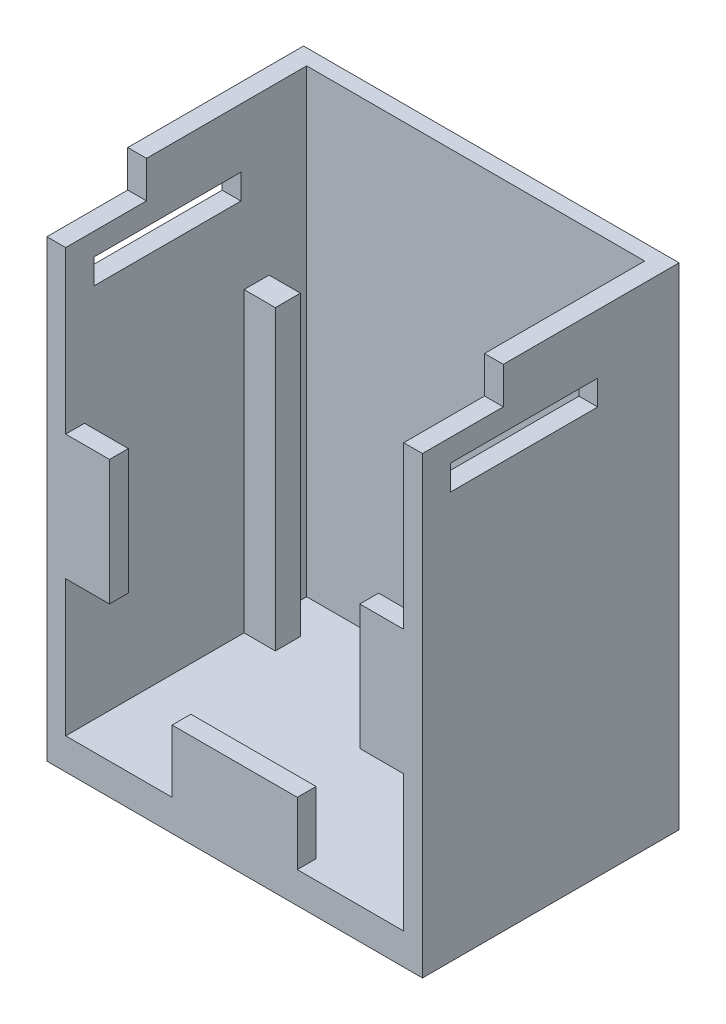
SolidWorks part; units mm, degrees
material "ABS"
ref_plane "Front Plane" through (0, 0, 0) normal (0, 0, 1) x (1, 0, 0)
ref_plane "Top Plane" through (0, 0, 0) normal (0, 1, 0) x (1, 0, 0)
ref_plane "Right Plane" through (0, 0, 0) normal (1, 0, 0) x (0, 0, -1)
sketch "Sketch1" plane through (0, 0, 0) normal (0, 0, 1) x (1, 0, 0)
  line L1 (15.24, -25.4) -> (-15.24, -25.4)
  line L2 (15.24, -25.4) -> (15.24, 15.24)
  line L3 (15.24, 15.24) -> (-15.24, 15.24)
  line L4 (-15.24, -25.4) -> (-15.24, 15.24)
  point P0 (0, 0)
  dimension "D1" = 30.48
  dimension "D2" = 40.64
extrude "Initial Block" add sketch "Sketch1" along normal blind 19.05 and the other way blind 1.778
sketch "Sketch2" plane through (0, 15.24, 0) normal (0, 1, 0) x (1, 0, 0)
  line L0 (15.24, 1.778) -> (-15.24, 1.778) construction
  line L1 (-13.716, 0.508) -> (13.716, 0.508)
  line L2 (-13.716, 0.508) -> (-13.716, -19.05)
  line L3 (-13.716, -19.05) -> (13.716, -19.05)
  line L4 (13.716, 0.508) -> (13.716, -19.05)
  line L5 (0, 1.778) -> (0, -14.7779) construction
  line L6 (15.24, -19.05) -> (-15.24, -19.05) construction
  point P9 (0, 1.778)
  point P11 (0, 0.508)
  point P12 (0, 0.508)
  dimension "D1" = 27.432
  dimension "D2" = 1.27
  dimension "D3" = 0
extrude "Initial Cut" cut sketch "Sketch2" against normal blind 38.1
ref_plane "Plane1" through (0, 0, 19.05) normal (0, 0, 1) x (1, 0, 0)
ref_plane "Plane2" through (0, 0, 0) normal (1, 0, 0) x (0, 0, -1)
sketch "Sketch20" plane through (0, 0, 19.05) normal (0, 0, 1) x (1, 0, 0)
  line L0 (-15.24, 9.398) -> (-15.24, -22.86) construction
  line L1 (-15.24, -22.86) -> (15.24, -22.86) construction
  line L2 (15.24, -22.86) -> (15.24, 9.398) construction
  line L3 (-15.24, -6.731) -> (15.24, -6.731) construction
  line L4 (15.24, 9.398) -> (-15.24, 9.398) construction
  line L5 (-15.24, -11.811) -> (-10.16, -11.811)
  line L6 (-15.24, -11.811) -> (-15.24, -1.651)
  line L7 (-15.24, -1.651) -> (-10.16, -1.651)
  line L8 (-10.16, -11.811) -> (-10.16, -1.651)
  line L9 (0, 9.398) -> (0, -22.86) construction
  line L10 (15.24, -11.811) -> (15.24, -1.651)
  line L11 (-5.08, -17.78) -> (5.08, -17.78)
  line L12 (-5.08, -17.78) -> (-5.08, -22.86)
  line L13 (-5.08, -22.86) -> (5.08, -22.86)
  line L14 (5.08, -17.78) -> (5.08, -22.86)
  line L15 (15.24, -11.811) -> (10.16, -11.811)
  line L16 (10.16, -11.811) -> (10.16, -1.651)
  line L17 (15.24, -1.651) -> (10.16, -1.651)
  line L19 (-13.716, -22.86) -> (13.716, -22.86) construction
  line L23 (-15.24, 15.24) -> (-15.24, -25.4) construction
  line L24 (15.24, -25.4) -> (15.24, 15.24) construction
  dimension "D1" = 10.16
  dimension "D2" = 5.08
  dimension "D3" = 10.16
  dimension "D4" = 5.08
  dimension "D5" = 5.08
  dimension "D6" = 10.16
extrude "Boss-Extrude1" add sketch "Sketch20" against normal blind 1.524
sketch "Sketch21" plane through (-13.716, 0, 0) normal (1, 0, 0) x (0, 0, -1)
  line L0 (-19.05, -1.651) -> (-19.05, 15.24) construction
  line L1 (-4.572, 1.27) -> (-2.54, 1.27)
  line L2 (-4.572, 1.27) -> (-4.572, -22.86)
  line L3 (-4.572, -22.86) -> (-2.54, -22.86)
  line L4 (-2.54, 1.27) -> (-2.54, -22.86)
  line L5 (0.508, 15.24) -> (-19.05, 15.24) construction
  line L6 (0.508, -22.86) -> (-19.05, -22.86) construction
  dimension "D1" = 2.032
  dimension "D2" = 14.478
  dimension "D3" = 13.97
  dimension "D4" = 0
extrude "Boss-Extrude2" add sketch "Sketch21" along normal blind 2.54 contours L4 L3 L2 L1
mirror "Mirror2" about plane through (0, 0, 0) normal (1, 0, 0) of "Boss-Extrude2"
sketch "Sketch27" plane through (15.24, 0, 0) normal (1, 0, 0) x (0, 0, -1)
  line L0 (-16.764, 9.652) -> (-4.826, 9.652)
  line L1 (-16.764, 9.652) -> (-16.764, 7.62)
  line L2 (-16.764, 7.62) -> (-4.826, 7.62)
  line L3 (-4.826, 9.652) -> (-4.826, 7.62)
  line L5 (-19.05, -25.4) -> (-19.05, 15.24) construction
  line L7 (1.778, -25.4) -> (-19.05, -25.4) construction
  dimension "D1" = 11.938
  dimension "D2" = 2.032
  dimension "D3" = 33.02
  dimension "D4" = 2.286
extrude "Cut-Extrude6" cut sketch "Sketch27" against normal up to next
mirror "Mirror6" about plane through (0, 0, 0) normal (1, 0, 0) of "Cut-Extrude6"
sketch "Sketch28" plane through (0, 0, 19.05) normal (0, 0, 1) x (1, 0, 0)
  line L0 (15.24, -25.4) -> (15.24, 15.24) construction
  line L1 (-15.24, 15.24) -> (15.24, 15.24)
  line L2 (-15.24, 15.24) -> (-15.24, 13.462)
  line L3 (-15.24, 13.462) -> (15.24, 13.462)
  line L4 (15.24, 15.24) -> (15.24, 13.462)
  dimension "D1" = 1.778
extrude "Cut-Extrude7" cut sketch "Sketch28" against normal through all
sketch "Sketch29" plane through (0, 0, 19.05) normal (0, 0, 1) x (1, 0, 0)
  line L0 (15.24, -25.4) -> (15.24, 13.462) construction
  line L1 (-15.24, 13.462) -> (15.24, 13.462)
  line L2 (-15.24, 13.462) -> (-15.24, 11.462)
  line L3 (-15.24, 11.462) -> (15.24, 11.462)
  line L4 (15.24, 13.462) -> (15.24, 11.462)
  dimension "D1" = 2
extrude "Cut-Extrude8" cut sketch "Sketch29" against normal blind 5.81
sketch "Sketch30" plane through (0, 13.462, 0) normal (0, 1, 0) x (1, 0, 0)
  line L0 (-15.24, -13.24) -> (-15.24, 1.778)
  line L1 (-15.24, 1.778) -> (15.24, 1.778)
  line L2 (15.24, 1.778) -> (15.24, -13.24)
  line L3 (15.24, -13.24) -> (13.716, -13.24)
  line L4 (13.716, -13.24) -> (13.716, 0.508)
  line L5 (13.716, 0.508) -> (-13.716, 0.508)
  line L6 (-13.716, 0.508) -> (-13.716, -13.24)
  line L7 (-13.716, -13.24) -> (-15.24, -13.24)
extrude "Boss-Extrude3" add sketch "Sketch30" along normal blind 0.99
sketch "Sketch31" plane through (0, 0, 13.24) normal (0, 0, 1) x (1, 0, 0)
  line L0 (15.24, 11.462) -> (15.24, 14.452) construction
  line L1 (-15.24, 14.452) -> (15.24, 14.452)
  line L2 (-15.24, 14.452) -> (-15.24, 11.462)
  line L3 (-15.24, 11.462) -> (15.24, 11.462)
  line L4 (15.24, 14.452) -> (15.24, 11.462)
  line L5 (13.716, 11.462) -> (15.24, 11.462) construction
extrude "Cut-Extrude9" cut sketch "Sketch31" against normal blind 0.75
